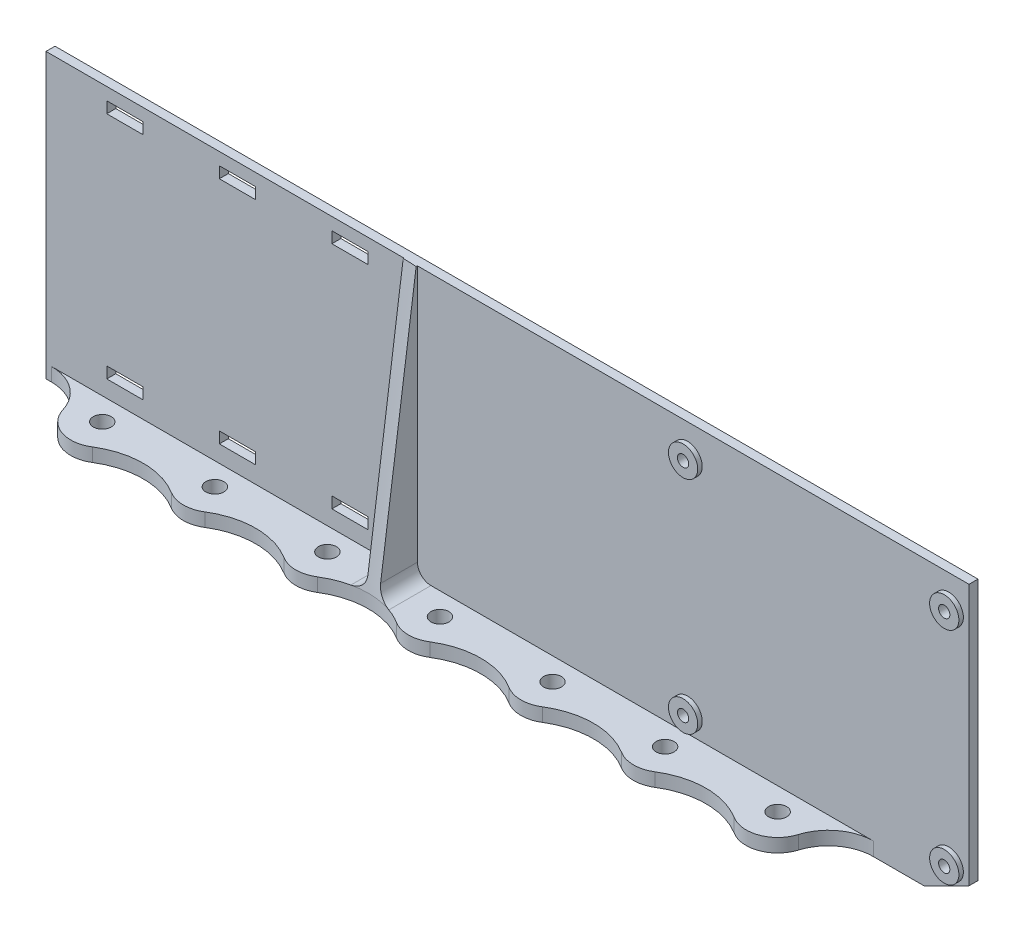
SolidWorks part; units mm, degrees
ref_plane "Front Plane" through (0, 0, 0) normal (0, 0, 1) x (1, 0, 0)
ref_plane "Top Plane" through (0, 0, 0) normal (0, 1, 0) x (1, 0, 0)
ref_plane "Right Plane" through (0, 0, 0) normal (1, 0, 0) x (0, 0, -1)
sketch "Sketch1" plane through (0, 0, 0) normal (0, 1, 0) x (1, 0, 0)
  line L0 (0, 0) -> (25, 0) construction
  line L1 (25, 0) -> (50, 0) construction
  line L2 (12.5, 0) -> (12.5, -20) construction
  line L3 (37.5, 0) -> (37.5, -20) construction
  line L4 (-4.899, 5) -> (54.899, 5)
  line L5 (25, 5) -> (25, 7) construction
  circle A0 centre (0, 0) radius 2
  circle A1 centre (25, 0) radius 2
  circle A2 centre (50, 0) radius 2
  circle A3 centre (0, 0) radius 7
  circle A4 centre (25, 0) radius 7
  circle A5 centre (50, 0) radius 7
  arc A6 (21.29, -5.936) -> (3.71, -5.936) centre (12.5, -20) ccw
  arc A7 (46.29, -5.936) -> (28.71, -5.936) centre (37.5, -20) ccw
  dimension "D1" = 4
  dimension "D2" = 25
  dimension "D3" = 5
  dimension "D6" = 20
  dimension "D7" = 2
  dimension "D4" = 5
  dimension "D5" = 5
extrude "Boss-Extrude1" add sketch "Sketch1" along normal blind 3 contours L4 A3 A0 | A6 A4 L4 A3 | L4 A4 A1 | A7 A5 L4 A4 | L4 A5 A2
sketch "Sketch2" plane through (0, 0, -5) normal (0, 0, -1) x (-1, 0, 0)
  line L0 (-25, 0) -> (-25, 7) construction
  line L1 (4.899, 0) -> (-54.899, 0) construction
  line L2 (-25, 3) -> (-25, 0) construction
  line L3 (-25, 56) -> (-25, 7) construction
  line L5 (37.5, 63) -> (-87.5, 63)
  line L6 (37.5, 63) -> (37.5, 0)
  line L7 (37.5, 0) -> (-87.5, 0)
  line L8 (-87.5, 63) -> (-87.5, 0)
  line L9 (37.5, 63) -> (-87.5, 0) construction
  line L10 (37.5, 0) -> (-87.5, 63) construction
  circle A0 centre (-25, 7) radius 1.25
  circle A1 centre (-83, 7) radius 1.25
  circle A2 centre (-83, 56) radius 1.25
  circle A3 centre (-25, 56) radius 1.25
  point P7 (-25, 31.5)
  dimension "D2" = 2.5
  dimension "D4" = 58
  dimension "D1" = 7
  dimension "D6" = 49
  dimension "D7" = 125
  dimension "D3" = 2
  dimension "D5" = 2
extrude "Boss-Extrude2" add sketch "Sketch2" along normal blind 2
sketch "Sketch6" plane through (-37.5, 0, 0) normal (-1, 0, 0) x (0, 0, 1)
  line L4 (-5, 0) -> (-5, 63)
  line L5 (-5, 63) -> (-7, 63)
  line L6 (-7, 63) -> (-7, 0)
  line L7 (-7, 0) -> (-5, 0)
  line L8 (-5, 0) -> (-5, 63)
  line L9 (-5, 63) -> (-7, 63)
  line L10 (-7, 63) -> (-7, 0)
  line L11 (-7, 0) -> (-5, 0)
  dimension "D1" = 0
extrude "Boss-Extrude6" add sketch "Sketch6" along normal blind 80
pattern_linear "LPattern1" count 5 spacing 25 along (-1, 0, 0) of "Boss-Extrude1"
fillet "Fillet1" radius 10 2 edges at (54.899, 1.5, -5) (-104.899, 1.5, -5)
chamfer "Chamfer1" distance 5 distance2 10 1 edges at (87.5, 0, -6)
sketch "Sketch3" plane through (0, 0, -5) normal (0, 0, 1) x (1, 0, 0)
  circle A0 centre (25, 7) radius 1.25 construction
  circle A1 centre (83, 7) radius 1.25 construction
  circle A2 centre (83, 56) radius 1.25 construction
  circle A3 centre (25, 56) radius 1.25 construction
  circle A4 centre (25, 7) radius 1.25
  circle A5 centre (83, 7) radius 1.25
  circle A6 centre (83, 56) radius 1.25
  circle A7 centre (25, 56) radius 1.25
  circle A8 centre (25, 56) radius 3.25
  circle A9 centre (83, 56) radius 3.25
  circle A10 centre (83, 7) radius 3.25
  circle A11 centre (25, 7) radius 3.25
  dimension "D1" = 2
extrude "Boss-Extrude3" add sketch "Sketch3" along normal blind 1
sketch "Sketch5" plane through (0, 0, -5) normal (0, 0, 1) x (1, 0, 0)
  line L0 (-35, 3) -> (-35, 63)
  line L1 (-116.2481, 3) -> (66.2481, 3) construction
  line L2 (-117.5, 63) -> (87.5, 63) construction
  line L3 (-35, 63) -> (-38, 63)
  line L4 (-38, 63) -> (-38, 3)
  line L5 (-38, 3) -> (-35, 3)
  circle A0 centre (25, 7) radius 1.25 construction
  dimension "D1" = 60
  dimension "D2" = 3
extrude "Boss-Extrude7" add sketch "Sketch5" along normal up to surface (8.4226 mm away)
chamfer "Chamfer3" distance 8.25 distance2 60 3 edges at (-38, 33, 3.4226) (-35, 33, 3.6046) (-36.4959, 63, 3.4455)
fillet "Fillet2" radius 3 3 edges at (-38, 3, -0.7887) (-35, 3, -0.6977) (-38, 31.9209, -0.5555)
sketch "Sketch7" plane through (0, 0, -5) normal (0, 0, 1) x (1, 0, 0)
  line L0 (-50, 3) -> (-50, 63) construction
  line L1 (-46.29, 3) -> (-53.71, 3) construction
  line L2 (-117.5, 63) -> (-38, 63) construction
  line L3 (-50, 3) -> (-50, 0) construction
  line L4 (-116.2481, 3) -> (-41, 3) construction
  line L5 (-54, 60.25) -> (-46, 60.25)
  line L6 (-54, 60.25) -> (-54, 57.75)
  line L7 (-54, 57.75) -> (-46, 57.75)
  line L8 (-46, 60.25) -> (-46, 57.75)
  line L9 (-54, 60.25) -> (-46, 57.75) construction
  line L10 (-54, 57.75) -> (-46, 60.25) construction
  line L11 (-54, 6.75) -> (-46, 6.75)
  line L12 (-54, 6.75) -> (-54, 9.25)
  line L13 (-54, 9.25) -> (-46, 9.25)
  line L14 (-46, 6.75) -> (-46, 9.25)
  line L15 (-54, 6.75) -> (-46, 9.25) construction
  line L16 (-54, 9.25) -> (-46, 6.75) construction
  point P8 (-50, 59)
  point P15 (-50, 8)
  dimension "D1" = 2.5
  dimension "D2" = 8
  dimension "D3" = 4
  dimension "D4" = 2.5
  dimension "D5" = 8
  dimension "D6" = 5
extrude "Cut-Extrude1" cut sketch "Sketch7" against normal through all
pattern_linear "LPattern2" count 3 spacing 25 along (-1, 0, 0) of "Cut-Extrude1"
